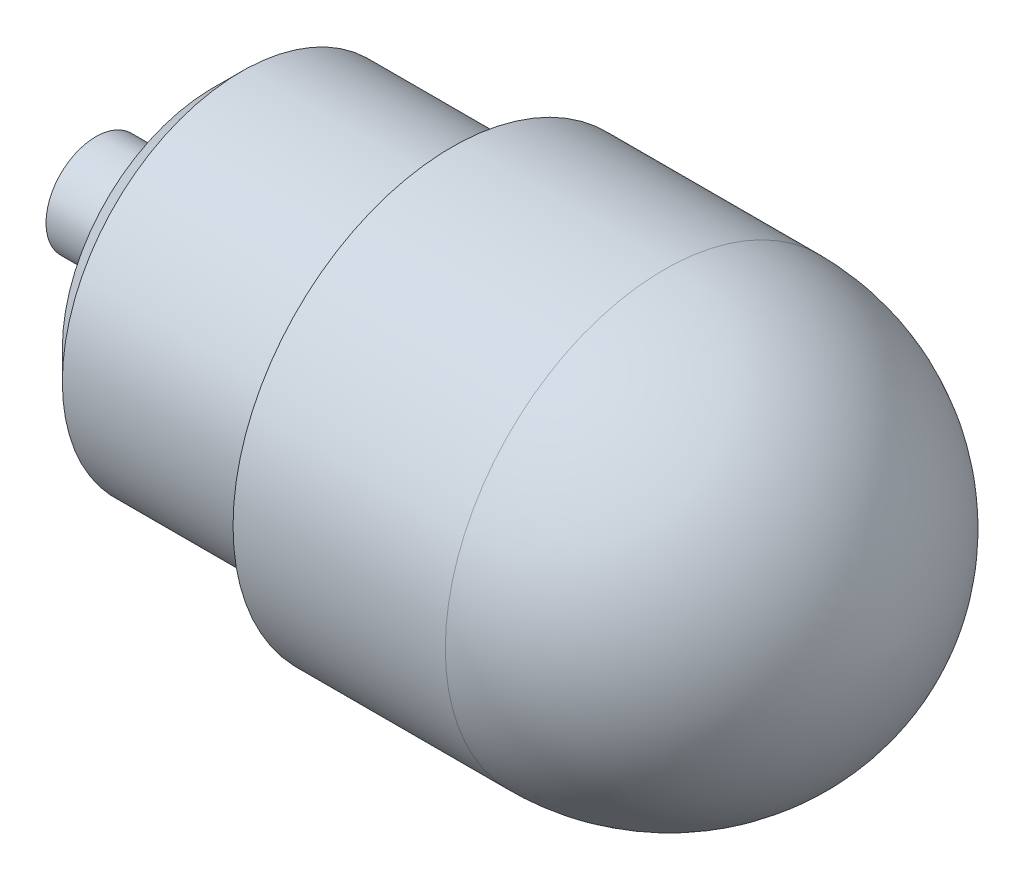
SolidWorks part; units mm, degrees
ref_plane "Front Plane" through (0, 0, 0) normal (0, 0, 1) x (1, 0, 0)
ref_plane "Top Plane" through (0, 0, 0) normal (0, 1, 0) x (1, 0, 0)
ref_plane "Right Plane" through (0, 0, 0) normal (1, 0, 0) x (0, 0, -1)
sketch "Sketch1" plane through (0, 0, 0) normal (0, 0, 1) x (1, 0, 0)
  line L0 (0, 0) -> (129.112, 0) construction
  line L1 (14.8357, 0) -> (14.8357, 6.3271)
  line L2 (14.8357, 6.3271) -> (29.6578, 6.3271)
  line L3 (29.6578, 6.3271) -> (29.6578, 19.0773)
  line L4 (29.6578, 19.0773) -> (33.3235, 22.743)
  line L5 (33.3235, 22.743) -> (60.0026, 22.743)
  line L6 (60.0026, 22.743) -> (60.0026, 27.7634)
  line L7 (60.0026, 27.7634) -> (86.9374, 27.7634)
  line L8 (14.8357, 0) -> (116.0405, 0)
  arc A0 (86.9374, 27.7634) -> (116.0405, 0) centre (86.9374, -1.372) cw
  point P13 (0, 0)
  point P14 (0, 0)
  point P15 (0, 0)
  point P16 (0, 0)
  point P17 (116.0405, 0)
revolve "Revolve1" add sketch "Sketch1" angle 360 about L0
